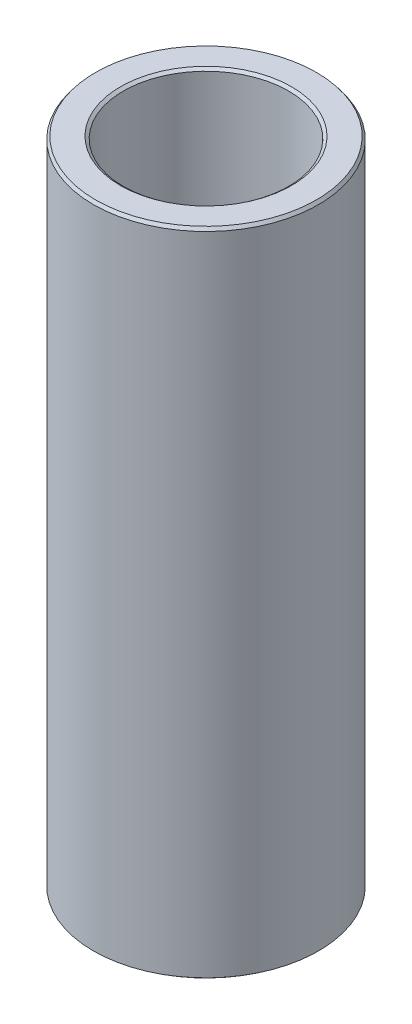
SolidWorks part; units mm, degrees
ref_plane "Front Plane" through (0, 0, 0) normal (0, 0, 1) x (1, 0, 0)
ref_plane "Top Plane" through (0, 0, 0) normal (0, 1, 0) x (1, 0, 0)
ref_plane "Right Plane" through (0, 0, 0) normal (1, 0, 0) x (0, 0, -1)
sketch "Sketch1" plane through (0, 0, 0) normal (0, 1, 0) x (1, 0, 0)
  circle A0 centre (0, 0) radius 47.5
  dimension "SLEEVE_OD" = 95
extrude "Boss-Extrude1" add sketch "Sketch1" along normal blind 274.749
sketch "Sketch2" plane through (0, 0, 0) normal (0, 1, 0) x (1, 0, 0)
  circle A0 centre (0, 0) radius 34.8544
  dimension "BORE_D" = 69.7089
extrude "Cut-Extrude1" cut sketch "Sketch2" along normal through all
chamfer "Chamfer1" distance 1.2448 angle 36.677 4 edges at (0, 274.749, 34.8544) (0, 0, 34.8544) (0, 0, 47.5) (0, 274.749, 47.5) first distance on face at (0, 274.749, 34.8544) first distance on face at (0, 0, 34.8544) first distance on face at (0, 274.749, 47.5)
